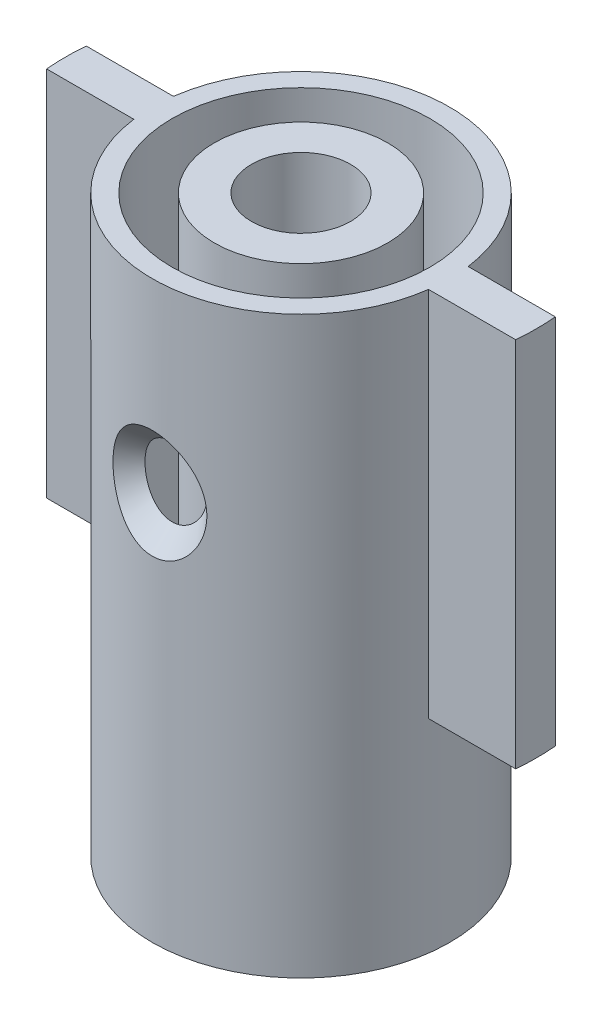
SolidWorks part; units mm, degrees
note: The reader was unsure of these and kept them because the rebuilt part matched: shared geometry of "Sketch1<3>", "Sketch1<4>".
ref_plane "Front Plane" through (0, 0, 0) normal (0, 0, 1) x (1, 0, 0)
ref_plane "Top Plane" through (0, 0, 0) normal (0, 1, 0) x (1, 0, 0)
ref_plane "Right Plane" through (0, 0, 0) normal (1, 0, 0) x (0, 0, -1)
sketch "Sketch1" plane through (0, 0, 0) normal (0, 1, 0) x (1, 0, 0)
  line L1 (3.5, -2.0207) -> (3.5, 2.0207)
  line L2 (3.5, 2.0207) -> (0, 4.0415)
  line L3 (0, 4.0415) -> (-3.5, 2.0207)
  line L4 (-3.5, 2.0207) -> (-3.5, -2.0207)
  line L5 (-3.5, -2.0207) -> (0, -4.0415)
  line L6 (0, -4.0415) -> (3.5, -2.0207)
  circle A0 centre (0, 0) radius 2
  circle A1 centre (0, 0) radius 3.5 construction
  circle A2 centre (0, 0) radius 3.5
  circle A3 centre (0, 0) radius 6
  dimension "D1" = 4
  dimension "D3" = 7
  dimension "D4" = 12
  dimension "D2" = 7
extrude "Boss-Extrude1" add sketch "Sketch1" along normal blind 20 contours A2 A0
extrude "Boss-Extrude2" add sketch "Sketch1<3>" against normal blind 3.2 separate body contours A3 L6 L5 L4 L3 L2 L1
sketch "Sketch1<3>" plane through (0, 0, 0) normal (0, 1, 0) x (1, 0, 0) same geometry as "Sketch1"
extrude "Boss-Extrude3" add sketch "Sketch1<4>" along normal blind 5 contours A2 L3 L4 | A2 L4 L5 | A2 L5 L6 | A2 L6 L1 | A2 L1 L2 | A2 L2 L3 | A3 L6 L5 L4 L3 L2 L1
sketch "Sketch1<4>" plane through (0, 0, 0) normal (0, 1, 0) x (1, 0, 0) same geometry as "Sketch1"
sketch "Sketch2" plane through (0, 5, 0) normal (0, 1, 0) x (1, 0, 0)
  line L0 (-5.9464, 0.8) -> (-9.4663, 0.8)
  line L1 (-9.4663, -0.8) -> (-5.9464, -0.8)
  line L2 (0, 0) -> (0, 9.5) construction
  line L3 (9.4663, -0.8) -> (5.9464, -0.8)
  line L4 (5.9464, 0.8) -> (9.4663, 0.8)
  circle A0 centre (0, 0) radius 5.2
  circle A1 centre (0, 0) radius 9.5
  circle A2 centre (0, 0) radius 6
  dimension "D1" = 10.4
  dimension "D2" = 19
  dimension "D3" = 12
  dimension "D4" = 1.6
extrude "Boss-Extrude4" add sketch "Sketch2" along normal blind 15
ref_plane "Plane1" through (0, 0, -6) normal (0, 0, -1) x (-1, 0, 0)
sketch "Sketch3" plane through (0, 0, -6) normal (0, 0, -1) x (-1, 0, 0)
  line L0 (9.4663, 20) -> (9.4663, 5) construction
  line L1 (-9.4663, 20) -> (-9.4663, 5) construction
  line L2 (9.4663, 20) -> (9.4663, 5) construction
  line L3 (-9.4663, 20) -> (-9.4663, 5) construction
  line L4 (-9.4663, 20) -> (9.4663, 5) construction
  point P4 (0, 12.5)
hole_wizard "CSK for M2 Flat Head Machine Screw1" positions "Sketch3" profile "Sketch5" countersink size "M2" standard "ANSI Metric"
sketch "Sketch5" plane through (0, 12.5, -6) normal (1, 0, 0) x (0, 1, 0)
  line L0 (0, 0) -> (0, 5)
  line L1 (0, 5) -> (1.2, 4.279)
  line L2 (1.2, 4.279) -> (1.2, 1)
  line L3 (1.2, 1) -> (2.2, 0)
  line L5 (2.2, 0) -> (0, 0)
  line L6 (-1.2, 1) -> (-2.2, 0) construction
  line L10 (0, 5) -> (-1.2, 4.279) construction
  line L11 (0, -6.35) -> (0, 107.95) construction
  dimension "Hole Dia." = 2.4
  dimension "Hole Depth" = 5
  dimension "Near C'Sink Dia." = 4.4
  dimension "Near C'Sink Angle" = 90
  dimension "Drill Angle" = 118
pattern_circular "CirPattern1" count 2 over 360 about axis through (0, 5, 0) along (0, -1, 0) of "CSK for M2 Flat Head Machine Screw1"
